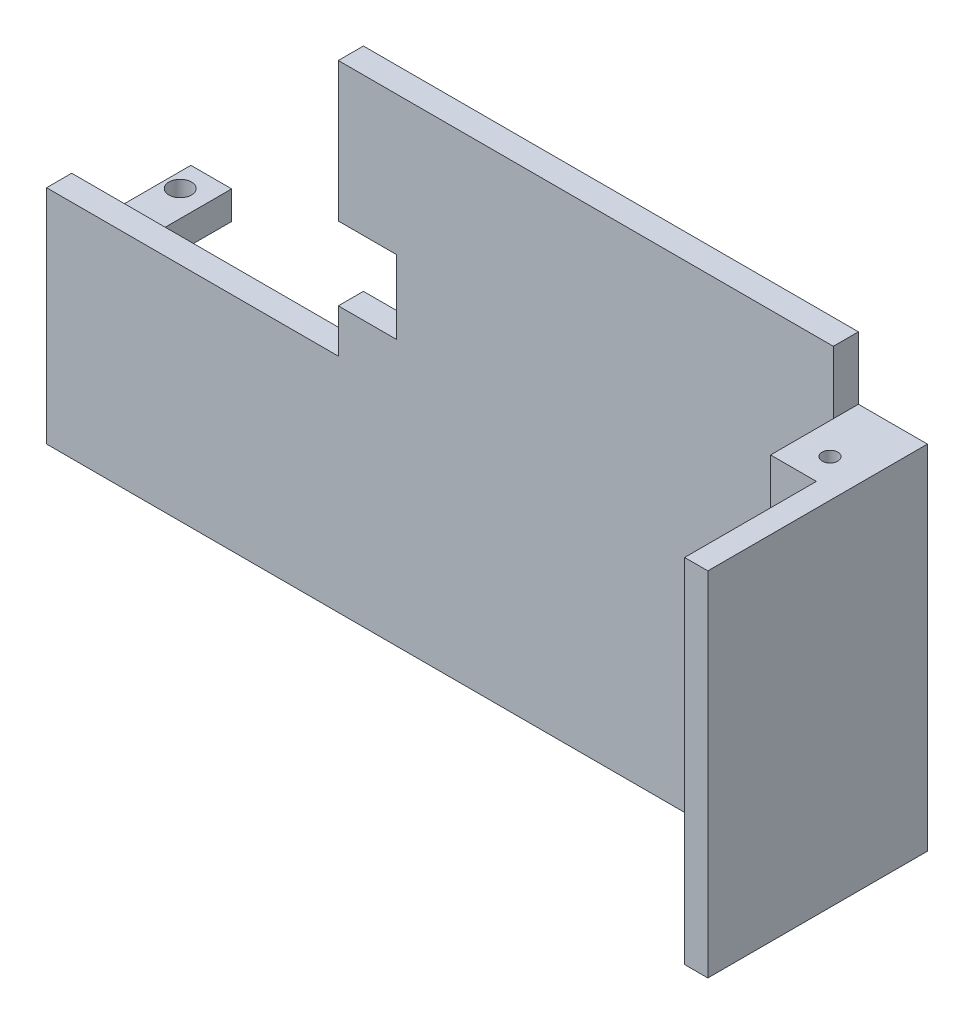
SolidWorks part; units mm, degrees
ref_plane "Front" through (0, 0, 0) normal (0, 0, 1) x (1, 0, 0)
ref_plane "Top" through (0, 0, 0) normal (0, 1, 0) x (1, 0, 0)
ref_plane "Right" through (0, 0, 0) normal (1, 0, 0) x (0, 0, -1)
sketch "Sketch1" plane through (0, 0, 0) normal (0, 1, 0) x (1, 0, 0)
  line L1 (0, 0) -> (78.9, 0)
  line L2 (0, 0) -> (0, 4)
  line L3 (0, 4) -> (78.9, 4)
  line L4 (78.9, 0) -> (78.9, 4)
  line L5 (78.9, 4) -> (88.9, 4)
  line L6 (78.9, 4) -> (78.9, -10)
  line L7 (78.9, -10) -> (88.9, -10)
  line L8 (88.9, 4) -> (88.9, -10)
  dimension "D1" = 4
  dimension "D2" = 10
  dimension "D3" = 88.9
  dimension "D4" = 10
extrude "Boss-Extrude1" add sketch "Sketch1" along normal blind 76.2 contours L1 L4 L3 L2 | L8 L5 L4 L6 L7 region at (39.45, 0, -2) region at (83.9, 0, 3)
sketch "Sketch2" plane through (0, 0, -4) normal (0, 0, -1) x (-1, 0, 0)
  line L1 (0, 0) -> (46.5, 0)
  line L2 (0, 0) -> (0, 26.8941)
  line L3 (0, 26.8941) -> (46.5, 26.8941)
  line L4 (46.5, 0) -> (46.5, 26.8941)
extrude "Boss-Extrude2" add sketch "Sketch2" against normal blind 4
sketch "Sketch5" plane through (0, 0, -4) normal (0, 0, -1) x (-1, 0, 0)
  line L0 (0, 76.2) -> (0, 26.8941) construction
  line L1 (0, 42.3336) -> (-9.286, 42.3336)
  line L2 (0, 42.3336) -> (0, 54.0406)
  line L3 (0, 54.0406) -> (-9.286, 54.0406)
  line L4 (-9.286, 42.3336) -> (-9.286, 54.0406)
extrude "Cut-Extrude2" cut sketch "Sketch5" against normal blind 5
sketch "Sketch6" plane through (0, 0, 0) normal (0, -1, 0) x (-1, 0, 0)
  line L0 (46.5, 4) -> (-88.9, 4) construction
  circle A0 centre (-83.8682, -5.5) radius 1.25
  dimension "D1" = 9.5
extrude "Cut-Extrude3" cut sketch "Sketch6" against normal blind 85
sketch "Sketch7" plane through (0, 0, 0) normal (0, -1, 0) x (1, 0, 0)
  line L0 (78.9, 10) -> (88.9, 10) construction
  line L5 (88.9, -4) -> (78.9, -4)
  line L6 (88.9, -4) -> (88.9, 10)
  line L7 (88.9, 10) -> (78.9, 10)
  line L8 (78.9, -4) -> (78.9, 10)
extrude "Cut-Extrude4" cut sketch "Sketch7" against normal blind 10
sketch "Sketch8" plane through (0, 76.2, 0) normal (0, 1, 0) x (1, 0, 0)
  line L0 (0, 4) -> (88.9, 4) construction
  line L5 (88.9, -10) -> (78.9, -10)
  line L6 (88.9, -10) -> (88.9, 4)
  line L7 (88.9, 4) -> (78.9, 4)
  line L8 (78.9, -10) -> (78.9, 4)
extrude "Cut-Extrude5" cut sketch "Sketch8" against normal blind 10
sketch "Sketch9" plane through (0, 66.2, 0) normal (0, 1, 0) x (1, 0, 0)
  line L0 (88.9, 4) -> (78.9, 4) construction
  line L1 (86.2, 4) -> (89.9, 4)
  line L2 (86.2, 4) -> (86.2, -31)
  line L3 (86.2, -31) -> (89.9, -31)
  line L4 (89.9, 4) -> (89.9, -31)
  line L5 (88.9, -10) -> (88.9, 4) construction
  dimension "D1" = 1
  dimension "D2" = 3.7
  dimension "D3" = 35
extrude "Boss-Extrude4" add sketch "Sketch9" against normal blind 56.2
sketch "Sketch10" plane through (0, 0, 0) normal (0, 0, 1) x (1, 0, 0)
  line L1 (0, 26.8941) -> (-46.5, 26.8941)
  line L2 (0, 26.8941) -> (0, 35.3902)
  line L3 (0, 35.3902) -> (-46.5, 35.3902)
  line L4 (-46.5, 26.8941) -> (-46.5, 35.3902)
extrude "Boss-Extrude5" add sketch "Sketch10" against normal blind 4
sketch "Sketch11" plane through (0, 0, -4) normal (0, 0, -1) x (-1, 0, 0)
  line L0 (-0.3, 26.98) -> (-0.3, 7.02) construction
  line L1 (-0.3, 26.98) -> (-6.9448, 26.98)
  line L2 (-0.3, 26.98) -> (-0.3, 22.4718)
  line L3 (-0.3, 22.4718) -> (-6.9448, 22.4718)
  line L4 (-6.9448, 26.98) -> (-6.9448, 22.4718)
  line L5 (40, 26.98) -> (40, 7.02) construction
  line L6 (40, 22.4718) -> (46.5, 22.4718)
  line L7 (40, 22.4718) -> (40, 26.98)
  line L8 (40, 26.98) -> (46.5, 26.98)
  line L9 (46.5, 22.4718) -> (46.5, 26.98)
  line L10 (46.5, 0) -> (46.5, 35.3902) construction
extrude "Boss-Extrude6" add sketch "Sketch11" along normal blind 19
sketch "Sketch12" plane through (0, 26.98, 0) normal (0, 1, 0) x (1, 0, 0)
  circle A0 centre (-44.15, 18.95) radius 1.8
  circle A1 centre (-44.15, 9.05) radius 1.8
  circle A2 centre (3.85, 18.95) radius 1.8
  circle A3 centre (3.85, 9.05) radius 1.8
extrude "Cut-Extrude6" cut sketch "Sketch12" against normal blind 19
